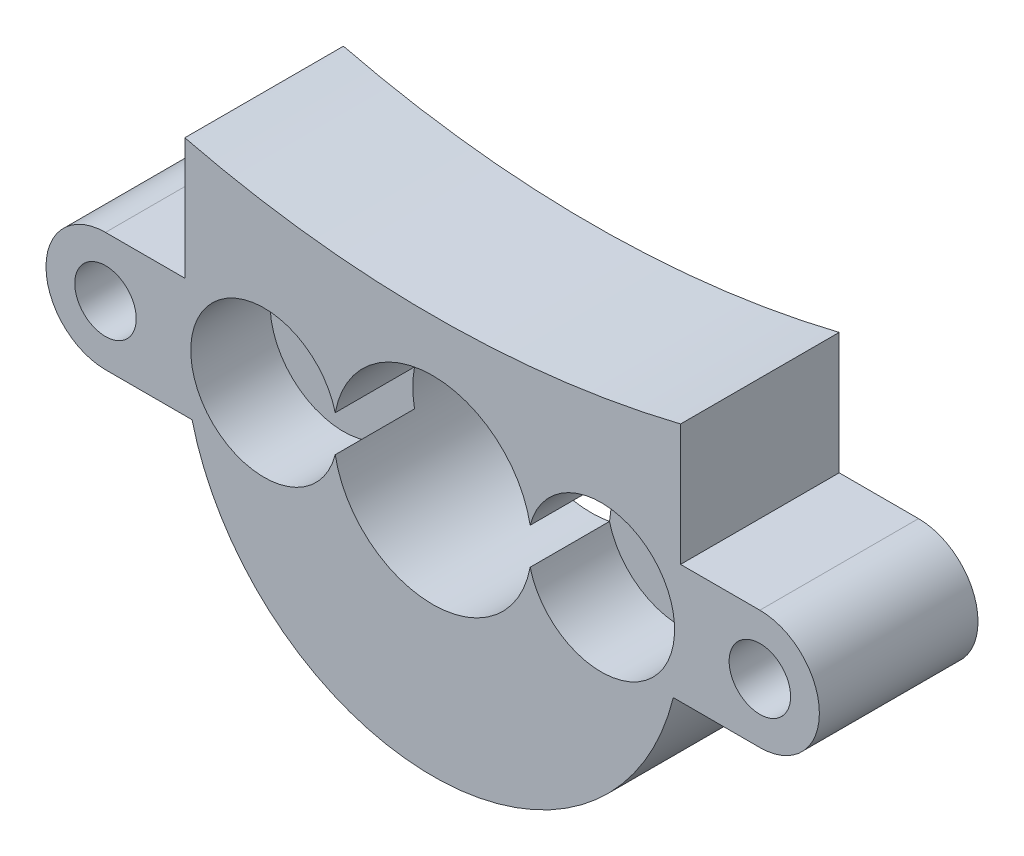
SolidWorks part; units mm, degrees
ref_plane "Front Plane" through (0, 0, 0) normal (0, 0, 1) x (1, 0, 0)
ref_plane "Top Plane" through (0, 0, 0) normal (0, 1, 0) x (1, 0, 0)
ref_plane "Right Plane" through (0, 0, 0) normal (1, 0, 0) x (0, 0, -1)
sketch "Sketch1" plane through (0, 0, 0) normal (0, 0, 1) x (1, 0, 0)
  line L0 (-8.5, 0) -> (8.5, 0) construction
  line L1 (0, 0) -> (0, 60) construction
  line L6 (-8.5, 0) -> (-16.5, 0) construction
  line L7 (8.5, 0) -> (16.5, 0) construction
  line L8 (-16.5, 3) -> (-12.5, 3)
  line L10 (16.5, 3) -> (12.5, 3)
  line L12 (-12.5, 9.1325) -> (-12.5, 3)
  line L13 (12.5, 3) -> (12.5, 9.1325)
  line L14 (16.5, -3) -> (12.1347, -3)
  line L15 (-16.5, -3) -> (-12.1347, -3)
  circle A0 centre (-8.5, 0) radius 1.55
  circle A1 centre (8.5, 0) radius 1.55
  circle A4 centre (0, 60) radius 52.3808 construction
  circle A8 centre (0, 0) radius 5
  arc A16 (-12.5, 0) -> (12.5, 0) centre (0, 0) ccw construction
  arc A17 (-12.5, 9.1325) -> (12.5, 9.1325) centre (0, 60) ccw
  circle A18 centre (-16.5, 0) radius 1.55
  circle A19 centre (16.5, 0) radius 1.55
  arc A21 (-16.5, 3) -> (-16.5, -3) centre (-16.5, 0) ccw
  arc A24 (16.5, 3) -> (16.5, -3) centre (16.5, 0) cw
  arc A25 (-12.1347, -3) -> (12.1347, -3) centre (0, 0) ccw
  point P4 (0, 0)
  point P13 (0, 7.6192)
  point P28 (0, 0)
extrude "Boss-Extrude1" add sketch "Sketch1" along normal blind 8
sketch "Sketch2" plane through (0, 0, 8) normal (0, 0, 1) x (1, 0, 0)
  circle A0 centre (-8.5, 0) radius 3.7
  circle A1 centre (8.5, 0) radius 3.7
extrude "Cut-Extrude1" cut sketch "Sketch2" against normal blind 4
